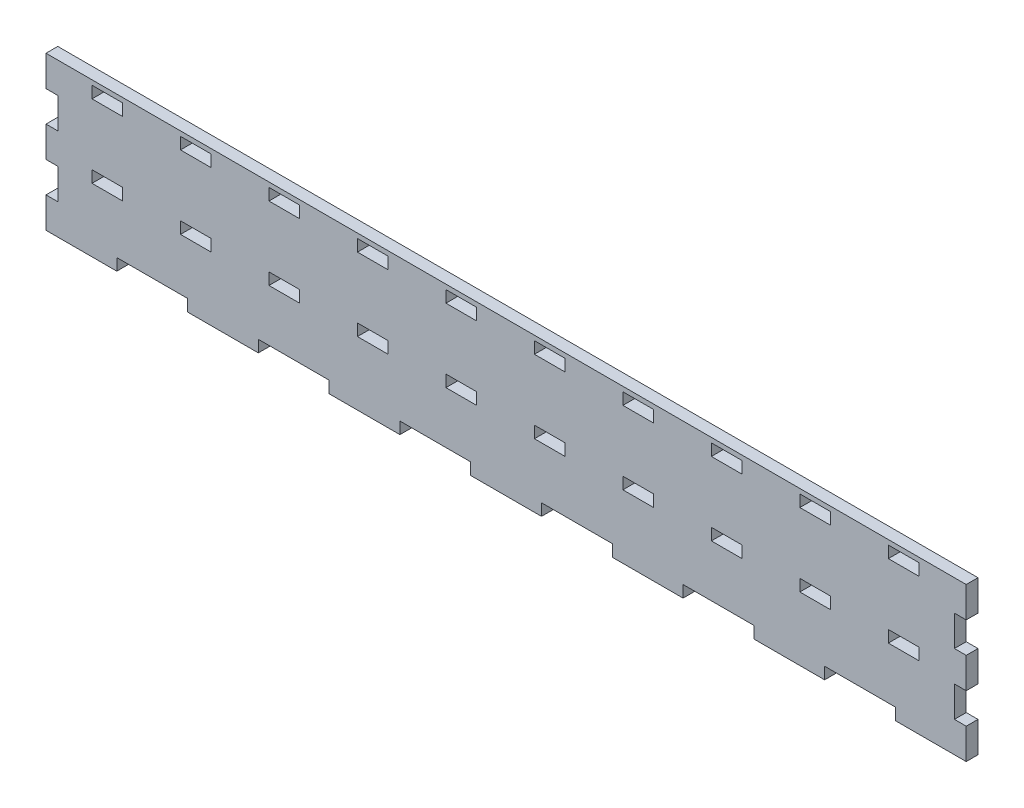
SolidWorks part; units mm, degrees
ref_plane "Plan de face" through (0, 0, 0) normal (0, 0, 1) x (1, 0, 0)
ref_plane "Plan de dessus" through (0, 0, 0) normal (0, 1, 0) x (1, 0, 0)
ref_plane "Plan de droite" through (0, 0, 0) normal (1, 0, 0) x (0, 0, -1)
sketch "Esquisse1" plane through (0, 0, 0) normal (0, 0, 1) x (1, 0, 0)
  line L1 (0, 0) -> (390, 0)
  line L2 (0, 0) -> (0, -65)
  line L3 (0, -65) -> (390, -65)
  line L4 (390, 0) -> (390, -65)
  dimension "D1" = 390
  dimension "D2" = 65
extrude "Boss.-Extru.1" add sketch "Esquisse1" along normal blind 5
sketch "Esquisse2" plane through (0, 0, 5) normal (0, 0, 1) x (1, 0, 0)
  line L0 (0, -65) -> (390, -65) construction
  line L1 (30, -65) -> (60, -65)
  line L2 (30, -65) -> (30, -60)
  line L3 (30, -60) -> (60, -60)
  line L4 (60, -65) -> (60, -60)
  line L5 (0, 0) -> (390, 0) construction
  line L6 (0, 0) -> (0, -65) construction
  dimension "D1" = 390
  dimension "D2" = 30
  dimension "D3" = 30
  dimension "D4" = 5
extrude "Enlèv. mat.-Extru.1" cut sketch "Esquisse2" against normal blind 5
pattern_linear "Répétition linéaire1" count 6 spacing 60 along (1, 0, 0) of "Enlèv. mat.-Extru.1"
sketch "Esquisse3" plane through (0, 0, 5) normal (0, 0, 1) x (1, 0, 0)
  line L0 (0, 0) -> (0, -65) construction
  line L1 (0, -52) -> (5, -52)
  line L2 (0, -52) -> (0, -39)
  line L3 (0, -39) -> (5, -39)
  line L4 (5, -52) -> (5, -39)
  line L5 (0, 0) -> (0, -65) construction
  line L6 (0, -65) -> (30, -65) construction
  dimension "D4" = 5
  dimension "D1" = 65
  dimension "D2" = 13
  dimension "D3" = 13
extrude "Enlèv. mat.-Extru.2" cut sketch "Esquisse3" against normal blind 5
pattern_linear "Répétition linéaire2" count 2 spacing 26 along (0, 1, 0) of "Enlèv. mat.-Extru.2"
ref_plane "Plan1" through (195, 0, 0) normal (-1, 0, 0) x (0, 0, 1)
mirror "Symétrie1" about plane through (195, 0, 0) normal (-1, 0, 0) of "Répétition linéaire2"
sketch "Esquisse4" plane through (0, 0, 5) normal (0, 0, 1) x (1, 0, 0)
  line L1 (57, -33) -> (70, -33)
  line L2 (57, -33) -> (57, -38)
  line L3 (57, -38) -> (70, -38)
  line L4 (70, -33) -> (70, -38)
  line L5 (57, -2) -> (70, -2)
  line L6 (0, -26) -> (0, -39) construction
  line L7 (60, -65) -> (90, -65) construction
  line L8 (57, -2) -> (57, -7)
  line L9 (57, -7) -> (70, -7)
  line L10 (70, -2) -> (70, -7)
  point P6 (63.5, -33)
  dimension "D3" = 13
  dimension "D2" = 5
  dimension "D1" = 70
  dimension "D4" = 32
  dimension "D5" = 26
  dimension "D6" = 5
extrude "Enlèv. mat.-Extru.3" cut sketch "Esquisse4" against normal blind 5
pattern_linear "Répétition linéaire3" count 2 spacing 37.5 along (-1, 0, 0) count 9 spacing 37.5 along (1, 0, 0) of "Enlèv. mat.-Extru.3"
equation "\"D1@Esquisse1\"=400-10"
equation "\"D2@Esquisse2\"=\"D1@Esquisse2\"/13"
equation "\"D3@Esquisse2\"=\"D1@Esquisse2\"/13"
equation "\"D2@Esquisse3\"=\"D1@Esquisse3\"/5"
equation "\"D3@Esquisse3\"=\"D1@Esquisse3\"/5"
equation "\"D6@Esquisse4\"=\"D2@Esquisse4\""
